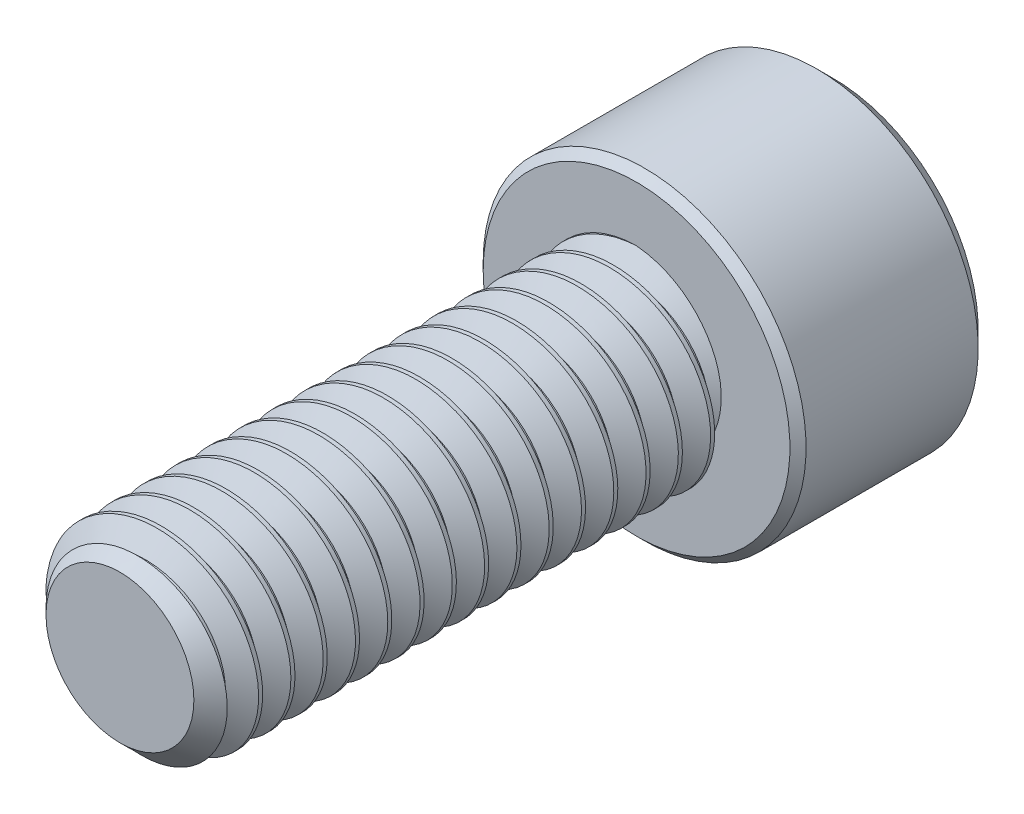
SolidWorks part; units mm, degrees
ref_plane "Front Plane" through (0, 0, 0) normal (0, 0, 1) x (1, 0, 0)
ref_plane "Top Plane" through (0, 0, 0) normal (0, 1, 0) x (1, 0, 0)
ref_plane "Right Plane" through (0, 0, 0) normal (1, 0, 0) x (0, 0, -1)
sketch "Sketch0" plane through (0, 0, 0) normal (1, 0, 0) x (0, 0, -1)
  line L0 (0, 0) -> (12.7, 0) construction
  point P2 (17.526, 0)
  point P4 (0, 0)
  dimension "D1" = 12.7
  dimension "D2" = 4.826
  dimension "Min Thread" = 0
sketch "Sketch1" plane through (0, 0, 0) normal (0, 0, 1) x (1, 0, 0)
  circle A0 centre (0, 0) radius 2.413
  dimension "OD" = 4.826
extrude "Extrude1" add sketch "Sketch1" against normal blind 12.7
sketch "Sketch2" plane through (0, 0, 0) normal (0, 0, 1) x (1, 0, 0)
  circle A0 centre (0, 0) radius 2.413 construction
  circle A1 centre (0, 0) radius 2.413
curve "Helix/Spiral1" pitch 0.7937 height 13.4937 turns 17 parameters "pitch"=0.7937
chamfer "Chamfer3" distance 0.5953 angle 45 1 edges at (2.413, 0, 0)
sketch "Sketch3" plane through (0, 0, 0) normal (1, 0, 0) x (0, 0, -1)
  line L0 (-0.6945, 2.413) -> (-0.3969, 1.8974)
  line L1 (-0.3969, 1.8974) -> (-0.2977, 1.8974)
  line L2 (-0.2977, 1.8974) -> (0, 2.413)
  line L3 (-0.6945, 2.413) -> (0, 2.413)
  line L4 (-0.3473, 2.413) -> (-0.3473, 1.8974) construction
  line L5 (-0.5457, 2.1552) -> (-0.1488, 2.1552) construction
  line L6 (0, 2.413) -> (0, -2.413) construction
  dimension "D1" = 0.0992
  dimension "D2" = 0.3969
  dimension "D3" = 60
sweep "Cut-Sweep1" cut profiles "Sketch3" path "Helix/Spiral1"
sketch "Sketch5" plane through (0, 0, 0) normal (1, 0, 0) x (0, 0, -1)
  line L0 (12.7, -1.9083) -> (12.7, 1.7217) construction
  line L1 (12.7, 2.413) -> (0, 2.413)
  line L2 (12.7, 2.413) -> (12.7, 0)
  line L3 (12.7, 0) -> (-0.8783, 0)
  line L4 (0, 0) -> (12.7, 0) construction
  line L5 (0, 2.413) -> (-0.8783, 0)
  line L6 (0, 0) -> (15.24, 0) construction
  dimension "D1" = 70
  dimension "D3" = 2.54
revolve "partially thread" [suppressed] add sketch "Sketch5" angle 360 about L6
sketch "Sketch6" plane through (0, 0, -12.7) normal (0, 0, -1) x (-1, 0, 0)
  circle A0 centre (0, 0) radius 3.9688
  dimension "head dia" = 7.9375
extrude "Extrude2" add sketch "Sketch6" along normal blind 4.826
sketch "Sketch7" plane through (0, 0, -17.526) normal (0, 0, -1) x (-1, 0, 0)
  line L1 (0, 2.2914) -> (-1.9844, 1.1457)
  line L2 (-1.9844, 1.1457) -> (-1.9844, -1.1457)
  line L3 (-1.9844, -1.1457) -> (0, -2.2914)
  line L4 (0, -2.2914) -> (1.9844, -1.1457)
  line L5 (1.9844, -1.1457) -> (1.9844, 1.1457)
  line L6 (1.9844, 1.1457) -> (0, 2.2914)
  circle A0 centre (0, 0) radius 1.9844 construction
  dimension "hex dia" = 3.9688
extrude "Cut-Extrude1" cut sketch "Sketch7" against normal blind 2.9766
sketch "Sketch8" plane through (0, 0, -17.526) normal (0, 0, -1) x (-1, 0, 0)
  circle A0 centre (0, 0) radius 2.2914
extrude "Cut-Extrude2" cut sketch "Sketch8" against normal through all draft 45
chamfer "Chamfer1" distance 0.3969 angle 45 1 edges at (-3.9688, 0, -17.526)
chamfer "Chamfer2" distance 0.1984 angle 45 1 edges at (-3.9688, 0, -12.7)
sketch "Sketch9" plane through (0, 0, 0) normal (1, 0, 0) x (0, 0, -1)
  line L0 (0, 2.413) -> (0, -2.413) construction
  line L1 (1.9844, 2.413) -> (1.9844, -2.413) construction
  line L2 (17.526, 3.9688) -> (17.526, -3.9688) construction
  line L3 (12.7, 3.9688) -> (12.7, -3.9688) construction
  line L4 (12.7, 3.7703) -> (12.7, -3.7703) construction
  line L5 (17.526, -3.5719) -> (17.526, 3.5719) construction
  line L6 (12.7, -3.9688) -> (12.7, 3.9688) construction
  line L7 (0, 1.8177) -> (0, -1.8177) construction
  line L8 (-0.6945, 2.413) -> (0, 2.413) construction
  line L9 (1.9844, 0) -> (0, 0) construction
  dimension "D1" = 1.9844
equation "\"D3@Helix/Spiral1\" = \"screw length@Extrude1\"+\"pitch@Helix/Spiral1\""
equation "\"D1@Sketch3\" = \"pitch@Helix/Spiral1\"*.125"
equation "\"D2@Sketch3\" = \"pitch@Helix/Spiral1\"*.5"
equation "\"D1@Cut-Extrude1\" = \"hex dia@Sketch7\"*.75"
equation "\"D1@Chamfer1\" = \"head dia@Sketch6\"*.05"
equation "\"D1@Sketch9\" = \"pitch@Helix/Spiral1\"*2.50"
equation "\"D1@Chamfer2\" = \"D1@Chamfer1\"/2"
equation "\"D1@Chamfer3\" = \"pitch@Helix/Spiral1\"*.750"
equation "\"D1@Sketch0\" = \"screw length@Extrude1\""
equation "\"D2@Sketch0\" = \"head depth@Extrude2\""
